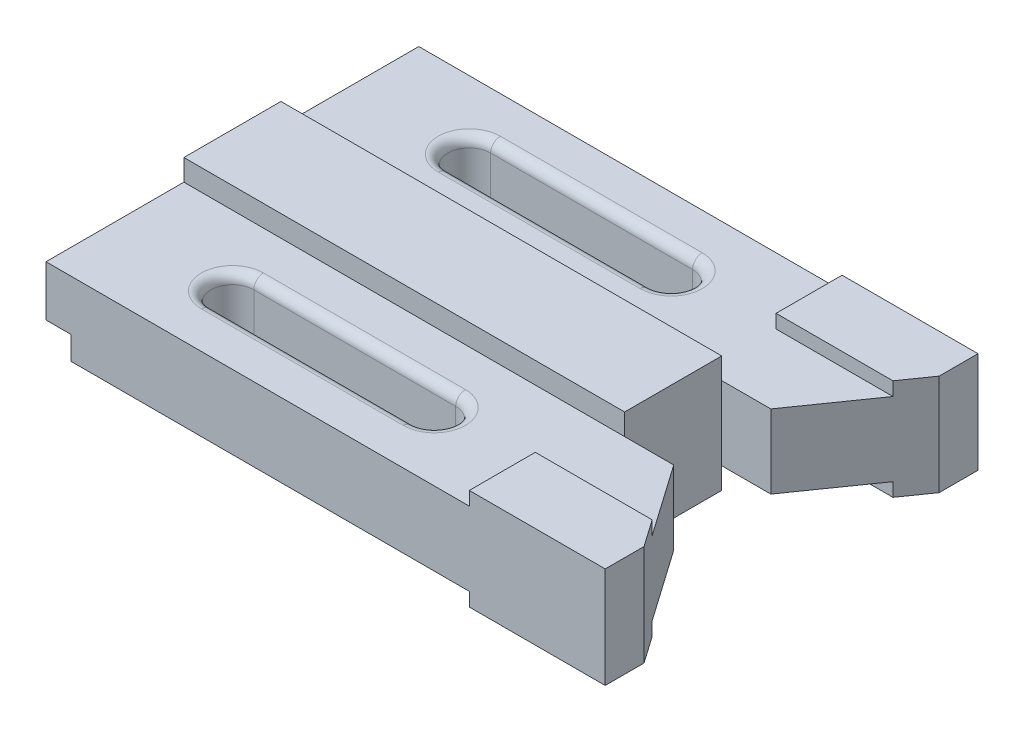
SolidWorks part; units mm, degrees
material "Alliage 1060"
ref_plane "Plan de face" through (0, 0, 0) normal (0, 0, 1) x (1, 0, 0)
ref_plane "Plan de dessus" through (0, 0, 0) normal (0, 1, 0) x (1, 0, 0)
ref_plane "Plan de droite" through (0, 0, 0) normal (1, 0, 0) x (0, 0, -1)
sketch "Esquisse1" plane through (0, 0, 0) normal (0, 1, 0) x (1, 0, 0)
  line L0 (0, 0) -> (-143.5103, 0) construction
  line L1 (0, -12.5) -> (0, 12.5)
  line L2 (-113.5, 12.5) -> (12.6447, 12.5)
  line L3 (12.6447, 12.5) -> (30.5, 38)
  line L4 (30.5, 38) -> (30.5, 48)
  line L5 (30.5, 48) -> (-113.5, 48)
  line L6 (-113.5, 48) -> (-113.5, -48)
  line L7 (-83, -30.5) -> (-31, -30.5) construction
  line L8 (-83, 30.5) -> (-31, 30.5) construction
  line L9 (-83, 36) -> (-31, 36)
  line L10 (-83, 25) -> (-31, 25)
  line L11 (25.5985, 31) -> (-4.5, 31)
  line L12 (-4.5, 31) -> (-4.5, 48)
  line L13 (-83, -36) -> (-31, -36)
  line L14 (-83, -25) -> (-31, -25)
  line L15 (-4.5, -31) -> (-4.5, -48)
  line L16 (25.5985, -31) -> (-4.5, -31)
  line L17 (30.5, -48) -> (-113.5, -48)
  line L18 (30.5, -38) -> (30.5, -48)
  line L19 (12.6447, -12.5) -> (30.5, -38)
  line L20 (-113.5, -12.5) -> (12.6447, -12.5)
  arc A0 (-83, 36) -> (-83, 25) centre (-83, 30.5) ccw
  arc A1 (-31, 25) -> (-31, 36) centre (-31, 30.5) ccw
  arc A2 (-83, -36) -> (-83, -25) centre (-83, -30.5) cw
  arc A3 (-31, -25) -> (-31, -36) centre (-31, -30.5) cw
  point P12 (-57, 30.5)
  point P24 (-57, -30.5)
  point P33 (-113.5, 0)
  dimension "D3" = 5.5
  dimension "D1" = 96
  dimension "D2" = 17.5
  dimension "D4" = 52
  dimension "D5" = 30.5
  dimension "D6" = 10
  dimension "D7" = 35.5
  dimension "D8" = 17
  dimension "D9" = 35
  dimension "D10" = 144
  dimension "D11" = 55
  dimension "D12" = 30.5
extrude "Boss.-Extru.1" add sketch "Esquisse1" along normal mid plane 30 contours L6 L20 L1 L2 region at (-56.75, 0, 0)
extrude "Boss.-Extru.2" add sketch "Esquisse1<3>" along normal offset from surface 5.5 and the other way offset from surface 5.5 contours L20 L6 L17 L15 L16 L19 L14 A3 L13 A2 | L11 L12 L5 L6 L2 L3 A1 L10 A0 L9 region at (6.3224, 0, 13.9356) region at (-56.75, 0, -13.9356) up to face at (-56.75, 15, 0) other way up to face at (-56.75, -15, 0)
sketch "Esquisse1<3>" plane through (0, 0, 0) normal (0, 1, 0) x (1, 0, 0) same geometry as "Esquisse1"
extrude "Boss.-Extru.3" add sketch "Esquisse1<4>" along normal mid plane 26 contours L12 L11 L3 L4 L5 | L19 L16 L15 L17 L18 region at (12.529, 0, 39.6831) region at (12.529, 0, -39.6831)
sketch "Esquisse1<4>" plane through (0, 0, 0) normal (0, 1, 0) x (1, 0, 0) same geometry as "Esquisse1"
sketch "Esquisse2" plane through (0, 0, 0) normal (0, 0, 1) x (1, 0, 0)
  line L0 (-113.5, 9.5) -> (-113.5, -9.5) construction
  line L1 (-113.5, -3.5) -> (-107, -3.5)
  line L2 (-113.5, -3.5) -> (-113.5, -15)
  line L3 (-113.5, -15) -> (-107, -15)
  line L4 (-107, -3.5) -> (-107, -15)
  line L5 (-113.5, -15) -> (0, -15) construction
  dimension "D1" = 11.5
  dimension "D2" = 6.5
extrude "Enlèv. mat.-Extru.1" cut sketch "Esquisse2" against normal through all and the other way through all
fillet "Congé1" radius 2.5 16 edges at (-25.5, -9.5, 30.5) (-57, -9.5, 25) (-88.5, -9.5, 30.5) (-57, -9.5, -36) (-88.5, -9.5, -30.5) (-57, -9.5, -25) (-57, 9.5, 36) (-25.5, 9.5, 30.5) (-57, 9.5, 25) (-57, 9.5, -36) (-25.5, 9.5, -30.5) (-57, 9.5, -25) (-57, -9.5, 36) (-25.5, -9.5, -30.5) (-88.5, 9.5, 30.5) (-88.5, 9.5, -30.5)
equation "\"A\" = 144"
equation "\"B\" = 52"
equation "\"C\"= 55deg"
equation "\"D4@Esquisse1\"=\"B\""
equation "\"D10@Esquisse1\"=\"A\""
equation "\"D11@Esquisse1\"=\"C\""
